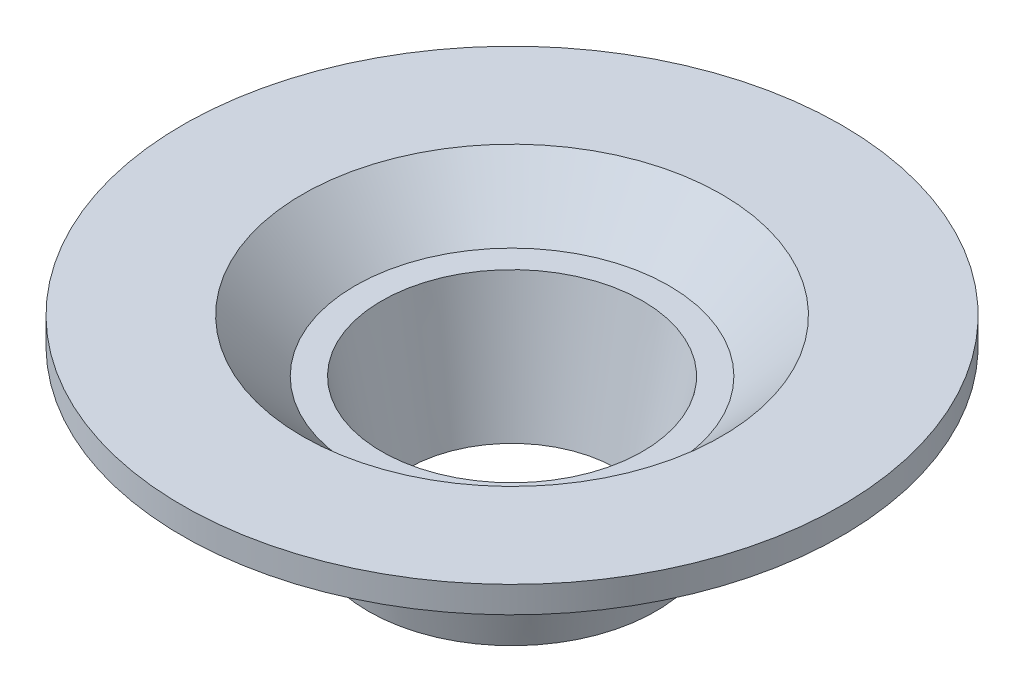
SolidWorks part; units mm, degrees
ref_plane "Front Plane" through (0, 0, 0) normal (0, 0, 1) x (1, 0, 0)
ref_plane "Top Plane" through (0, 0, 0) normal (0, 1, 0) x (1, 0, 0)
ref_plane "Right Plane" through (0, 0, 0) normal (1, 0, 0) x (0, 0, -1)
sketch "Sketch1" plane through (0, 0, 0) normal (0, 0, 1) x (1, 0, 0)
  line L0 (0, 0) -> (0, 5) construction
  line L5 (4.95, 5) -> (5.95, 5)
  line L6 (5.95, 5) -> (7.95, 7)
  line L7 (7.95, 7) -> (12.5, 7)
  line L8 (12.5, 7) -> (12.5, 6)
  line L9 (12.5, 6) -> (10.5, 6)
  line L10 (10.5, 6) -> (8.5, 4)
  line L11 (8.5, 4) -> (6.25, 4)
  line L12 (6.25, 4) -> (5.45, 0)
  line L13 (5.45, 0) -> (3.95, 0)
  line L14 (3.95, 0) -> (4.95, 5)
  point P12 (0, 0)
  point P14 (8.9594, 8.6821)
  point P15 (13.9291, 4.9864)
  point P16 (7.6016, 5)
  point P17 (9.6454, 6.5822)
  point P18 (8.6095, 4.3844)
  point P19 (12.1372, 12.2238)
  point P20 (0, 0)
  point P21 (11.3533, 7.2122)
  point P22 (10.7373, 12.3078)
  dimension "D2" = 5
  dimension "D3" = 25
  dimension "D4" = 2
  dimension "D5" = 2
  dimension "D6" = 1
  dimension "D7" = 2
  dimension "D8" = 4
  dimension "D9" = 12.5
  dimension "D10" = 1.5
  dimension "D11" = 9.9
  dimension "D12" = 1
  dimension "D13" = 7.9
revolve "Revolve1" add sketch "Sketch1" angle 360 about L0
